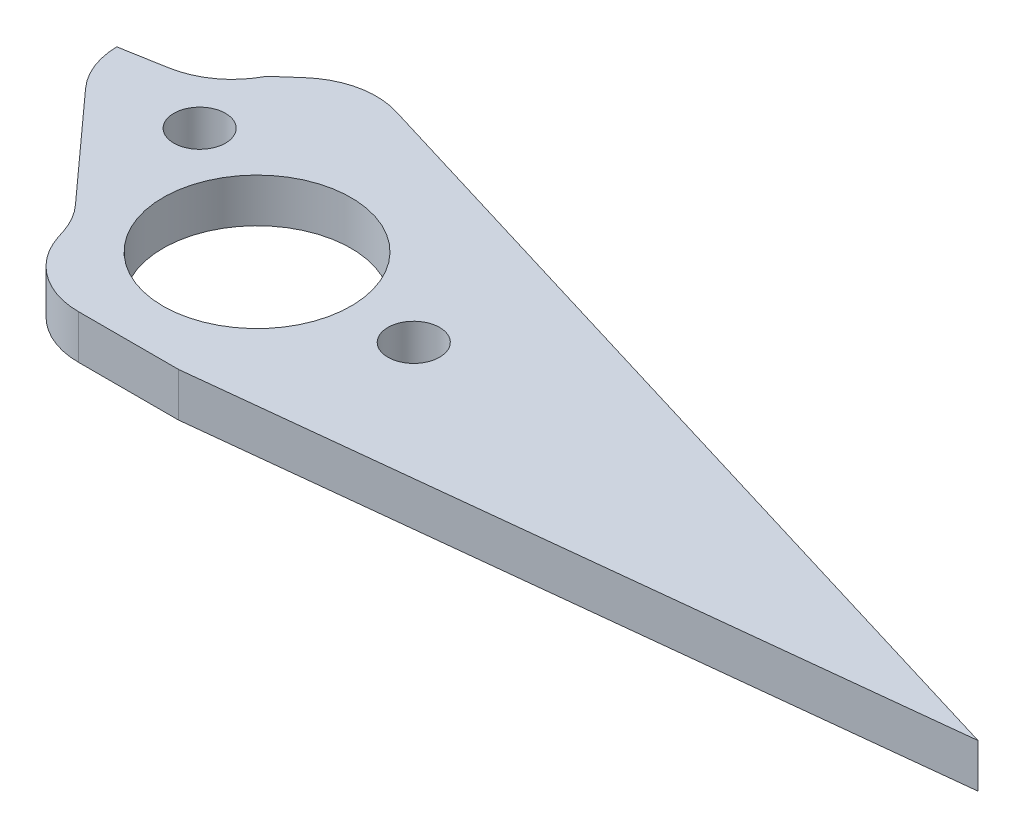
SolidWorks part; units mm, degrees
material "Plain Carbon Steel"
ref_plane "Front Plane" through (0, 0, 0) normal (0, 0, 1) x (1, 0, 0)
ref_plane "Top Plane" through (0, 0, 0) normal (0, 1, 0) x (1, 0, 0)
ref_plane "Right Plane" through (0, 0, 0) normal (1, 0, 0) x (0, 0, -1)
sketch "Sketch1" plane through (0, 0, 0) normal (0, 1, 0) x (1, 0, 0)
  line L9 (-9.4, 10) -> (-6, 13)
  line L11 (-9.4, 8) -> (-15.8, 8)
  line L12 (-15.8, 8) -> (-15.8, 5)
  line L14 (-9.4, 10) -> (-9.4, 8)
  line L18 (4, -9) -> (-6, -9)
  line L22 (-15.8, 5) -> (-7.6609, -4)
  line L23 (-7.6609, -4) -> (-6, -9)
  line L24 (-6, 13) -> (50, -4)
  line L25 (50, -4) -> (4, -9)
  circle A0 centre (0, 0) radius 6
  dimension "D1" = 12
  dimension "D3" = 6
  dimension "D4" = 10
  dimension "D5" = 50
  dimension "D6" = 5
  dimension "D10" = 3
  dimension "D11" = 2
  dimension "D12" = 6.4
  dimension "D13" = 3
  dimension "D14" = 5
  dimension "D17" = 15.8
  dimension "D20" = 9
extrude "Boss-Extrude3" add sketch "Sketch1" along normal blind 2.8
fillet "Fillet1" radius 5 4 edges at (-6, 1.4, -13) (-15.8, 1.4, -5) (-7.6609, 1.4, 4) (-6, 1.4, 9)
sketch "Sketch5" plane through (0, 0, 0) normal (0, -1, 0) x (1, 0, 0)
  line L0 (0, 0) -> (10, 0) construction
  line L1 (0, 0) -> (-8.6603, -5) construction
  circle A0 centre (10, 0) radius 1.65
  circle A1 centre (-8.6603, -5) radius 1.65
  dimension "D1" = 3.3
  dimension "D2" = 10
  dimension "D4" = 150
  dimension "D3" = 2
extrude "Cut-Extrude2" cut sketch "Sketch5" against normal blind 10
chamfer "Chamfer1" distance 6.5 angle 10 1 edges at (-15.8, 1.4, -8) first distance on face at (-12.6, 1.4, -8)
fillet "Fillet2" radius 5 1 edges at (-9.4, 1.4, -7.9824)
